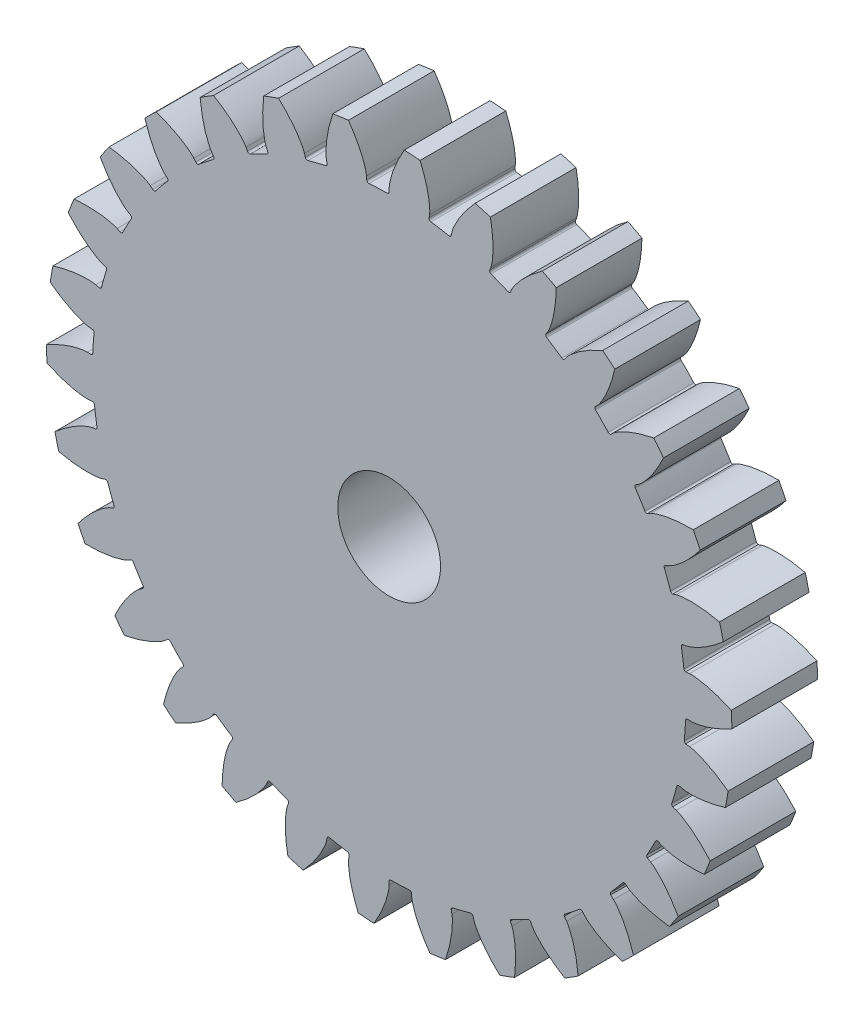
SolidWorks part; units mm, degrees
ref_plane "Alzado" through (0, 0, 0) normal (0, 0, 1) x (1, 0, 0)
ref_plane "Planta" through (0, 0, 0) normal (0, 1, 0) x (1, 0, 0)
ref_plane "Vista lateral" through (0, 0, 0) normal (1, 0, 0) x (0, 0, -1)
sketch "Croquis1" plane through (0, 0, 0) normal (0, 0, 1) x (1, 0, 0)
  line L0 (0, 0) -> (131.0885, 0) construction
  line L1 (0, 0) -> (0, 30) construction
  line L2 (0, 0) -> (12.4587, 12.4587) construction
  line L3 (12.4587, 12.4587) -> (2.6737, 22.2437) construction
  line L4 (0, 0) -> (11.3254, 13.4971) construction
  line L5 (11.3254, 13.4971) -> (1.9027, 21.4038) construction
  line L6 (0, 0) -> (10.106, 14.4328) construction
  line L7 (10.106, 14.4328) -> (1.2895, 20.6062) construction
  line L8 (0, 0) -> (8.8096, 15.2587) construction
  line L9 (8.8096, 15.2587) -> (0.8202, 19.8714) construction
  line L10 (0, 0) -> (7.4462, 15.9685) construction
  line L11 (7.4462, 15.9685) -> (0.4787, 19.2175) construction
  line L12 (0, 0) -> (6.0261, 16.5567) construction
  line L13 (6.0261, 16.5567) -> (0.2468, 18.6602) construction
  line L14 (0, 0) -> (4.5602, 17.0189) construction
  line L15 (4.5602, 17.0189) -> (0.1047, 18.2127) construction
  line L16 (0, 0) -> (3.0595, 17.3516) construction
  line L17 (3.0595, 17.3516) -> (0.0311, 17.8856) construction
  line L18 (0, 0) -> (1.5356, 17.5522) construction
  line L19 (1.5356, 17.5522) -> (0.0039, 17.6862) construction
  circle A0 centre (0, 0) radius 17.6192 construction
  circle A1 centre (0, 0) radius 17.3038 construction
  circle A2 centre (0, 0) radius 20 construction
  circle A3 centre (0, 0) radius 18.75 construction
  spline S0 degree 3 poles (0, 17.6192) (0.003, 17.7087) (0.0309, 17.9084) (0.1107, 18.2574) (0.255, 18.7048) (0.4889, 19.2621) (0.8326, 19.916) (1.5096, 20.9709) (2.1682, 21.7377) (2.6737, 22.2437) knots 0 0 0 0 0.049384 0.111113 0.197533 0.308643 0.444446 0.604939 1 1 1 1
  point P3 (87.284, 1.25)
  point P4 (102.0506, 30)
  point P5 (119.8936, 20)
  point P29 (0, 17.6192)
  dimension "Diámetro de paso (D)" = 37.5
  dimension "Diámetro de raiz" = 34.6075
  dimension "D1" = 40
  dimension "D2" = 35.2385
  dimension "Módulo (m)" = 1.25
  dimension "Número de dientes (N)" = 30
  dimension "Ángulo de presión (AP)" = 20
  dimension "D3" = 45
  dimension "D4" = 13.8381
  dimension "D5" = 40
  dimension "D6" = 12.3005
  dimension "D7" = 35
  dimension "D8" = 10.763
  dimension "D9" = 9.2254
  dimension "D10" = 30
  dimension "D11" = 25
  dimension "D12" = 7.6878
  dimension "D13" = 20
  dimension "D14" = 6.1503
  dimension "D15" = 15
  dimension "D16" = 4.6127
  dimension "D17" = 10
  dimension "D18" = 3.0751
  dimension "D19" = 5
  dimension "D20" = 1.5376
sketch "Croquis2" plane through (0, 0, 0) normal (0, 0, 1) x (1, 0, 0)
  line L0 (56.3227, 9.5882) -> (76.5884, 9.5882) construction
  line L1 (0, 17.3911) -> (0, 17.6192)
  line L2 (0, 0) -> (0.3802, 25.5087) construction
  line L3 (0, 0) -> (3.1082, 25.8589) construction
  line L4 (0, 0) -> (32.6464, 0) construction
  line L5 (0, 0) -> (131.0885, 0) construction
  line L6 (0, 0) -> (1.6991, 25.221) construction
  line L7 (2.3325, 17.2754) -> (2.3632, 17.46)
  line L8 (57.5292, -20.4598) -> (78.7754, -20.4598) construction
  circle A0 centre (0, 0) radius 17.3038 construction
  circle A1 centre (0, 0) radius 20 construction
  arc A2 (-0.1185, 17.3033) -> (2.4382, 17.1311) centre (0, 0) ccw
  arc A3 (1.8037, 19.9185) -> (0.8841, 19.9804) centre (0, 0) ccw
  circle A4 centre (0, 0) radius 18.75 construction
  circle A5 centre (0, 0) radius 3
  arc A6 (2.3325, 17.2754) -> (2.4382, 17.1311) centre (2.4558, 17.2549) ccw
  arc A7 (0, 17.3911) -> (-0.1185, 17.3033) centre (-0.1193, 17.4283) cw
  spline S0 degree 3 poles (3999.154, -11.1559) (22.4729, -2.4419) (-1.6764, 10.4482) (0.1107, 18.2574) (0.255, 18.7048) (0.4889, 19.2621) (0.8326, 19.916) (24.6889, 57.0873) (266.2192, -59.859) (-3996.4932, 54.198) knots -4.222676 -4.222676 -4.222676 -4.222676 0.049384 0.111113 0.197533 0.308643 0.444446 0.604939 24.668661 24.668661 24.668661 24.668661 only from (0, 17.6192) to (2.6737, 22.2437) construction
  spline S1 degree 3 poles (0, 17.6192) (0.003, 17.7087) (0.0309, 17.9084) (0.1107, 18.2574) (0.255, 18.7048) (0.4889, 19.2621) (0.7168, 19.6957) (0.8626, 19.9442) (0.8841, 19.9804) knots 0 0 0 0 0.049384 0.111113 0.197533 0.308643 0.444446 0.467706 0.467706 0.467706 0.467706
  spline S2 degree 3 poles (2.3632, 17.46) (2.3722, 17.5491) (2.3714, 17.7508) (2.339, 18.1073) (2.2561, 18.57) (2.0991, 19.1536) (1.9314, 19.6139) (1.8202, 19.8797) (1.8037, 19.9185) knots 0 0 0 0 0.049384 0.111113 0.197533 0.308643 0.444446 0.467706 0.467706 0.467706 0.467706
  point P8 (0.2795, 18.7479)
  point P13 (28.0519, 1.9635)
  point P22 (68.2533, 14.5882)
  point P25 (68.2533, 9.5402)
  dimension "Diámetro del cubo" = 6
  dimension "Redondeo" = 0.125
  dimension "Espesor del diente (T)" = 1.9635
  dimension "D1" = 6
  dimension "D2" = 3
  dimension "Espesor del engrane" = 5
  dimension "dientes" = 30
extrude "Saliente-Extruir1" add sketch "Croquis2" along normal blind 5
pattern_circular "MatrizC6" count 30 over 360 about axis through (0, 0, 5) along (0, 0, -1) of "Saliente-Extruir1"
equation "\"Diámetro de paso (D)@Croquis1\"=\"Módulo (m)@Croquis1\"*\"Número de dientes (N)@Croquis1\""
equation "\"Diámetro de raiz@Croquis1\"=(\"Diámetro de paso (D)@Croquis1\")-((2.314)*(\"Módulo (m)@Croquis1\"))"
equation "\"D1@Croquis1\"=(\"Diámetro de paso (D)@Croquis1\")+((2)*(\"Módulo (m)@Croquis1\"))"
equation "\"D2@Croquis1\"=(\"Diámetro de paso (D)@Croquis1\")*(cos( \"Ángulo de presión (AP)@Croquis1\"))"
equation "\"D4@Croquis1\"=(\"D2@Croquis1\"/(2))*((\"D3@Croquis1\")*(PI)/(180))"
equation "\"D6@Croquis1\"=(\"D2@Croquis1\"/(2))*((\"D5@Croquis1\")*(PI)/(180))"
equation "\"D8@Croquis1\"=(\"D2@Croquis1\"/(2))*((\"D7@Croquis1\")*(PI)/(180))"
equation "\"D9@Croquis1\"=(\"D2@Croquis1\"/(2))*((\"D10@Croquis1\")*(PI)/(180))"
equation "\"D12@Croquis1\"=(\"D2@Croquis1\"/(2))*((\"D11@Croquis1\")*(PI)/(180))"
equation "\"D14@Croquis1\"=(\"D2@Croquis1\"/(2))*((\"D13@Croquis1\")*(PI)/(180))"
equation "\"D16@Croquis1\"=(\"D2@Croquis1\"/(2))*((\"D15@Croquis1\")*(PI)/(180))"
equation "\"D18@Croquis1\"=(\"D2@Croquis1\"/(2))*((\"D17@Croquis1\")*(PI)/(180))"
equation "\"D20@Croquis1\"=(\"D2@Croquis1\"/(2))*((\"D19@Croquis1\")*(PI)/(180))"
equation "\"Espesor del diente (T)@Croquis2\"=(1.5708)*(\"Módulo (m)@Croquis1\")"
equation "\"D1@Croquis2\"=(\"Espesor del diente (T)@Croquis2\"/(\"Diámetro de paso (D)@Croquis1\"/2))*(180/PI)"
equation "\"D2@Croquis2\"=\"D1@Croquis2\"/2"
equation "\"D1@Saliente-Extruir1\"=\"Espesor del engrane@Croquis2\""
equation "\"dientes@Croquis2\"=\"Número de dientes (N)@Croquis1\""
equation "\"Redondeo@Croquis2\"=\"Módulo (m)@Croquis1\"*(0.1)"
equation "\"D1@MatrizC6\"=\"Número de dientes (N)@Croquis1\""
